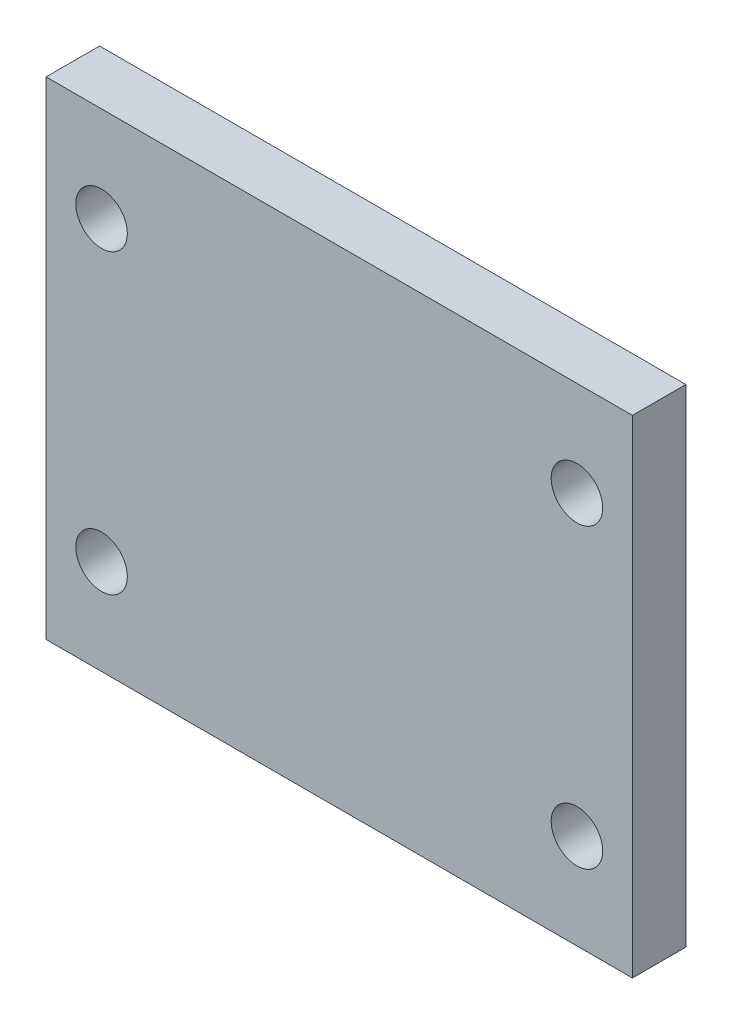
SolidWorks part; units mm, degrees
ref_plane "Front Plane" through (0, 0, 0) normal (0, 0, 1) x (1, 0, 0)
ref_plane "Top Plane" through (0, 0, 0) normal (0, 1, 0) x (1, 0, 0)
ref_plane "Right Plane" through (0, 0, 0) normal (1, 0, 0) x (0, 0, -1)
sketch "Sketch1" plane through (0, 0, 0) normal (0, 0, 1) x (1, 0, 0)
  line L1 (148, -123) -> (-148, -123)
  line L2 (148, -123) -> (148, 123)
  line L3 (148, 123) -> (-148, 123)
  line L4 (-148, -123) -> (-148, 123)
  line L5 (148, -123) -> (-148, 123) construction
  line L6 (148, 123) -> (-148, -123) construction
  circle A0 centre (-120, 75) radius 13 construction
  circle A1 centre (120, 75) radius 13 construction
  circle A2 centre (120, -75) radius 13 construction
  circle A3 centre (-120, -75) radius 13 construction
  circle A4 centre (-120, 75) radius 13
  circle A5 centre (120, 75) radius 13
  circle A6 centre (120, -75) radius 13
  circle A7 centre (-120, -75) radius 13
  point P0 (0, 0)
  dimension "D1" = 296
  dimension "D2" = 246
extrude "Extrude1" add sketch "Sketch1" along normal blind 27
